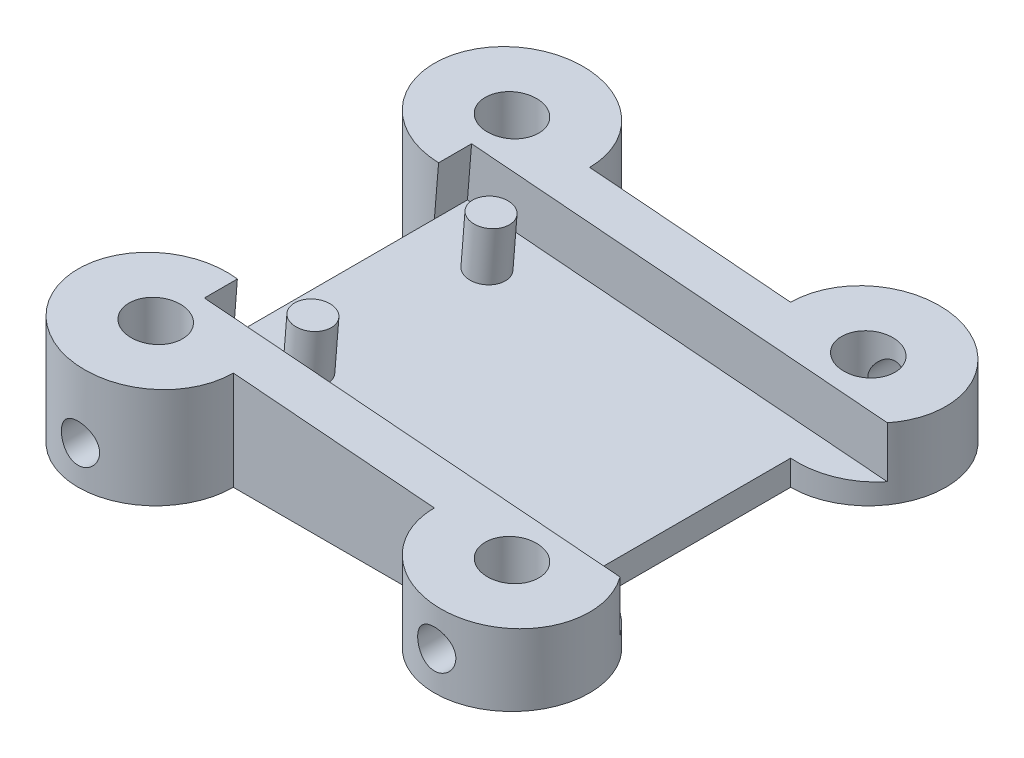
SolidWorks part; units mm, degrees
ref_plane "Front Plane" through (0, 0, 0) normal (0, 0, 1) x (1, 0, 0)
ref_plane "Top Plane" through (0, 0, 0) normal (0, 1, 0) x (1, 0, 0)
ref_plane "Right Plane" through (0, 0, 0) normal (1, 0, 0) x (0, 0, -1)
sketch "Sketch1" plane through (0, 0, 0) normal (0, 1, 0) x (1, 0, 0)
  line L0 (14, 28) -> (14, 0) construction
  line L1 (0, 0) -> (28, 0)
  line L2 (0, 0) -> (0, 28)
  line L3 (0, 28) -> (28, 28)
  line L4 (28, 0) -> (28, 28)
  line L5 (0, 14) -> (28, 14) construction
  point P9 (14, 14)
  dimension "D1" = 28
extrude "Boss-Extrude1" add sketch "Sketch1" along normal blind 8.2747
sketch "Sketch2" plane through (0, 0, 0) normal (0, 0, 1) x (1, 0, 0)
  line L0 (0, 8.2747) -> (28, 6)
  line L1 (0, 8.2747) -> (28, 8.2747) construction
  line L2 (28, 8.2747) -> (28, 0) construction
  line L3 (0, 8.2747) -> (28, 8.2747)
  line L4 (28, 8.2747) -> (28, 6)
  dimension "D2" = 6
  dimension "D3" = 4.644
extrude "Cut-Extrude1" cut sketch "Sketch2" against normal through all
sketch "Sketch3" plane through (0.6678, 8.2205, 0) normal (0.081, 0.9967, 0) x (0.9967, -0.081, 0)
  line L0 (-0.67, 28) -> (-0.67, 0) construction
  line L1 (-0.67, 3.5) -> (49.33, 3.5)
  line L2 (-0.67, 3.5) -> (-0.67, 24.5)
  line L3 (-0.67, 24.5) -> (49.33, 24.5)
  line L4 (49.33, 3.5) -> (49.33, 24.5)
  point P9 (-0.67, 14)
  point P10 (-0.67, 14)
  dimension "D1" = 21
  dimension "D2" = 50
extrude "Cut-Extrude2" cut sketch "Sketch3" against normal blind 4
ref_plane "Plane1" through (0, 8.2747, 0) normal (0, 1, 0) x (1, 0, 0)
sketch "Sketch11" plane through (0.3439, 4.2336, 0) normal (0.081, 0.9967, 0) x (0.9967, -0.081, 0)
  line L0 (27.7472, 24.5) -> (-0.3451, 24.5) construction
  line L1 (27.7472, 24.5) -> (27.7472, 3.5) construction
  line L2 (-0.3451, 3.5) -> (27.7472, 3.5) construction
  line L3 (27.7472, 24.5) -> (-0.3451, 24.5) construction
  line L4 (27.7472, 24.5) -> (27.7472, 3.5) construction
  line L5 (-0.3451, 3.5) -> (27.7472, 3.5) construction
  line L6 (13.7011, 3) -> (13.7011, 50003) construction
  line L7 (24.633, 14) -> (-49975.367, 14) construction
  circle A2 centre (4.7011, 21) radius 1.45
  circle A3 centre (4.7011, 7) radius 1.45
  point P6 (13.7011, 3.5)
  point P9 (27.7472, 14)
  dimension "D4" = 2.9
  dimension "D5" = 9
  dimension "D6" = 7
extrude "Boss-Extrude2" add sketch "Sketch11" along normal blind 4
sketch "Sketch12" plane through (0, 8.2747, 0) normal (0, 1, 0) x (1, 0, 0)
  line L0 (0, 3.5) -> (0, 24.5) construction
  line L1 (0, 3.5) -> (28, 3.5) construction
  line L2 (0, 3.5) -> (0, 24.5) construction
  line L3 (0, 3.5) -> (28, 3.5) construction
  line L4 (0, 14) -> (50000, 14) construction
  line L5 (14, 4) -> (14, 50004) construction
  circle A0 centre (14, 14) radius 7
  point P7 (0, 14)
  point P10 (14, 3.5)
  dimension "D1" = 14
sketch "Sketch13" plane through (0, 0, 0) normal (0, -1, 0) x (1, 0, 0)
  line L0 (0, 0) -> (28, 0) construction
  line L1 (28, 0) -> (28, -28) construction
  line L2 (28, -28) -> (0, -28) construction
  line L3 (0, -28) -> (0, 0) construction
  line L4 (0, 0) -> (28, 0) construction
  line L5 (28, 0) -> (28, -28) construction
  line L6 (28, -28) -> (0, -28) construction
  line L7 (0, -28) -> (0, 0) construction
  line L8 (0, -14) -> (28, -14) construction
  line L9 (14, -28) -> (14, 0) construction
  circle A0 centre (0, 0) radius 2.1
  circle A1 centre (28, 0) radius 2.1
  circle A2 centre (28, -28) radius 2.1
  circle A3 centre (0, -28) radius 2.1
  dimension "D1" = 4.2
  dimension "D2" = 2
  dimension "D3" = 2
extrude "Cut-Extrude5" cut sketch "Sketch13" against normal through all
sketch "Sketch14" plane through (0, 0, 0) normal (0, -1, 0) x (1, 0, 0)
  line L0 (28, -3.5) -> (28, -2.1) construction
  line L1 (2.1, -28) -> (25.9, -28) construction
  line L2 (0, -3.5) -> (0, -24.5) construction
  circle A0 centre (0, 0) radius 2.1 construction
  circle A1 centre (0, 0) radius 2.1 construction
  circle A2 centre (0, 0) radius 6.1
  circle A3 centre (0, 0) radius 2.1
  circle A4 centre (28, 0) radius 2.1
  circle A5 centre (28, 0) radius 6.1
  circle A6 centre (28, -28) radius 2.1
  circle A7 centre (28, -28) radius 6.1
  circle A8 centre (0, -28) radius 2.1
  circle A9 centre (0, -28) radius 6.1
  dimension "D1" = 4
  dimension "D4" = 4.2
  dimension "D2" = 2
  dimension "D3" = 2
extrude "Boss-Extrude3" add sketch "Sketch14" against normal up to surface (8.2747 mm away) up to face at (14, 7.1374, -25.9884)
sketch "Sketch15" plane through (0, 0, -28) normal (0, 0, -1) x (-1, 0, 0)
  line L0 (-21.9, 0) -> (-6.1, 0) construction
  line L1 (-21.9, 0) -> (-0.9, 0) construction
  line L4 (-14, 7.1374) -> (-14, 0) construction
  line L5 (-6.1, 7.7791) -> (-21.9, 6.4956) construction
  circle A0 centre (-28, 3) radius 1.5
  circle A1 centre (0, 3) radius 1.5
  point P4 (-28, 0)
  dimension "D1" = 3
  dimension "D2" = 3
extrude "Cut-Extrude6" cut sketch "Sketch15" along normal through all
sketch "Sketch16" plane through (0, 0, 0) normal (0, 0, 1) x (1, 0, 0)
  circle A0 centre (0, 3) radius 1.5 construction
  circle A1 centre (28, 3) radius 1.5 construction
  circle A2 centre (0, 3) radius 1.5
  circle A3 centre (28, 3) radius 1.5
extrude "Cut-Extrude7" cut sketch "Sketch16" along normal through all
sketch "Sketch18" plane through (0.6678, 8.2205, 0) normal (0.081, 0.9967, 0) x (0.9967, -0.081, 0)
  line L5 (-0.67, 3.5) -> (27.238, 3.5) construction
  line L8 (4.3424, 3.5) -> (22.4098, 3.5) construction
  line L9 (4.3424, 3.5) -> (22.4098, 3.5) construction
  line L22 (4.6674, 24.5) -> (-0.3451, 24.5)
  line L37 (7.4098, 3.5) -> (37.4098, 3.5)
  line L38 (7.4098, 3.5) -> (7.4098, 24.5)
  line L39 (7.4098, 24.5) -> (37.4098, 24.5)
  line L40 (37.4098, 3.5) -> (37.4098, 24.5)
  line L42 (-0.3451, 24.5) -> (-0.3451, 21.9)
  line L46 (-0.3451, 6.1) -> (-0.3451, 3.5)
  line L47 (-0.3451, 3.5) -> (4.6674, 3.5)
  line L49 (4.3424, 24.5) -> (22.4098, 24.5) construction
  ellipse E1 centre (-0.3451, 28) end of major axis (5.775, 28) minor radius 6.1 (-0.3451, 21.9) -> (4.6674, 24.5) ccw construction
  ellipse E2 centre (-0.3451, 28) end of major axis (5.775, 28) minor radius 6.1 (-0.3451, 21.9) -> (4.6674, 24.5) ccw
  ellipse E3 centre (-0.3451, 0) end of major axis (5.775, 0) minor radius 6.1 (4.6674, 3.5) -> (-0.3451, 6.1) ccw construction
  ellipse E4 centre (-0.3451, 0) end of major axis (5.775, 0) minor radius 6.1 (4.6674, 3.5) -> (-0.3451, 6.1) ccw
  point P7 (22.4098, 3.5)
  dimension "D1" = 30
extrude "Cut-Extrude8" cut sketch "Sketch18" against normal up to surface (4 mm away) up to face at (6.4748, 3.7355, -21)
equation "\"TrackLength\"= 150"
equation "\"MarbleWidth\"= 13"
equation "\"MarbleTrackWidth\"= \"MarbleWidth\" - 1"
equation "\"TrackWidth\"= \"MarbleTrackWidth\" + ( 2 * 4 )"
equation "\"MarbleTrackLength\"= \"TrackLength\" - ( 2 * 8 )"
equation "\"MountWidth\"= \"TrackWidth\" + 6"
equation "\"D1@Sketch1\"=\"MountWidth\" + 2"
equation "\"D1@Boss-Extrude1\"=\"RampHeight\""
equation "\"RampDepth\"=6"
equation "\"RampAngle\"= 5"
equation "\"RampHeight\"= ( \"MountWidth\" * tan ( \"RampAngle\" ) ) + \"RampDepth\""
equation "\"D1@Sketch3\"=\"TrackWidth\" + 1"
equation "\"MountWidth\"= \"TrackWidth\" + 10"
equation "\"MountLength\"=66.6651"
